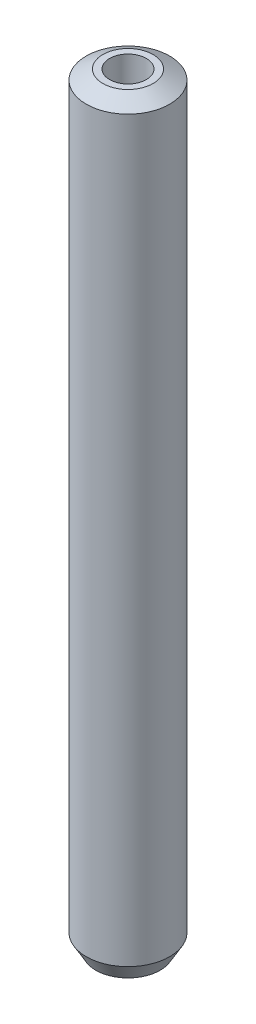
SolidWorks part; units mm, degrees
ref_plane "Front Plane" through (0, 0, 0) normal (0, 0, 1) x (1, 0, 0)
ref_plane "Top Plane" through (0, 0, 0) normal (0, 1, 0) x (1, 0, 0)
ref_plane "Right Plane" through (0, 0, 0) normal (1, 0, 0) x (0, 0, -1)
sketch "Sketch1" plane through (0, 0, 0) normal (0, 1, 0) x (1, 0, 0)
  circle A0 centre (0, 0) radius 17.5
  dimension "SHAFT_OD" = 35
extrude "Boss-Extrude1" add sketch "Sketch1" along normal blind 320.4677
sketch "Sketch2" plane through (0, 0, 0) normal (0, 1, 0) x (1, 0, 0)
  circle A0 centre (0, 0) radius 7.7065
  dimension "BORE_D" = 15.4131
extrude "Cut-Extrude1" cut sketch "Sketch2" along normal through all
chamfer "Chamfer1" distance 4.0204 angle 60 2 edges at (0, 320.4677, 17.5) (0, 0, 17.5) first distance on face at (0, 320.4677, 17.5) first distance on face at (0, 0, 7.7065)
